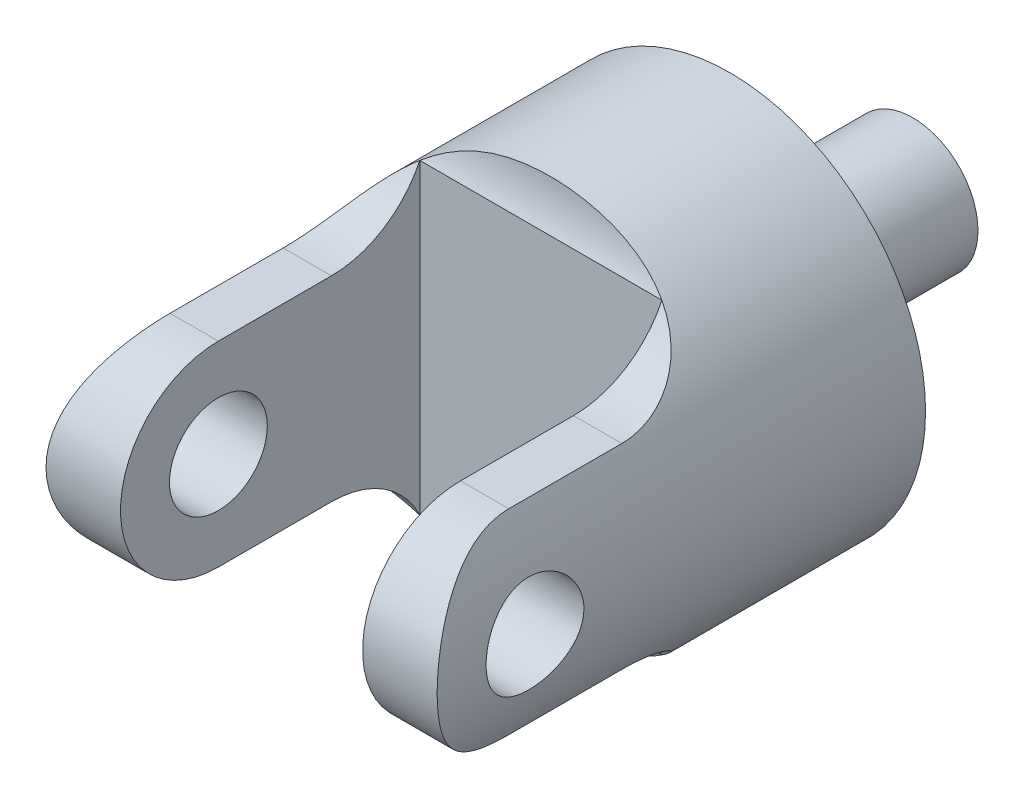
SolidWorks part; units mm, degrees
ref_plane "Front Plane" through (0, 0, 0) normal (0, 0, 1) x (1, 0, 0)
ref_plane "Top Plane" through (0, 0, 0) normal (0, 1, 0) x (1, 0, 0)
ref_plane "Right Plane" through (0, 0, 0) normal (1, 0, 0) x (0, 0, -1)
sketch "Sketch1" plane through (0, 0, 0) normal (0, 0, 1) x (1, 0, 0)
  circle A0 centre (0, 0) radius 6.35
  circle A1 centre (0, 0) radius 19.05
  dimension "D1" = 12.7
  dimension "D2" = 38.1
extrude "Boss-Extrude1" add sketch "Sketch1" along normal blind 47.57
extrude "Boss-Extrude2" add sketch "Sketch1<3>" along normal blind 18.42 and the other way blind 17.81 contours A0 region at (0, 0, 0)
sketch "Sketch1<3>" plane through (0, 0, 0) normal (0, 0, 1) x (1, 0, 0) same geometry as "Sketch1"
sketch "Sketch2" plane through (0, 0, 0) normal (0, 1, 0) x (1, 0, 0)
  line L0 (-11.79, -47.57) -> (11.79, -47.57)
  line L1 (-11.79, -47.57) -> (-11.79, -18.42)
  line L2 (11.79, -47.57) -> (11.79, -18.42)
  line L3 (-11.79, -18.42) -> (11.79, -18.42)
  line L4 (-19.05, -47.57) -> (19.05, -47.57) construction
  line L5 (19.05, 0) -> (-19.05, 0) construction
  dimension "D1" = 11.79
  dimension "D2" = 23.58
  dimension "D3" = 18.42
extrude "Cut-Extrude1" cut sketch "Sketch2" against normal through all both and the other way through all
sketch "Sketch3" plane through (0, 0, 0) normal (1, 0, 0) x (0, 0, -1)
  line L0 (0, 0) -> (-50000, 0) construction
  line L1 (-38.04, 9.53) -> (-36.8521, 9.53)
  line L2 (-50.2999, -9.53) -> (-38.04, -9.53)
  line L3 (-38.04, 9.53) -> (-68.1539, 9.53)
  line L4 (-68.0946, 9.165) -> (-59.6951, 20.2106)
  line L5 (-59.6951, 20.2106) -> (-27.0245, 19.06)
  line L6 (-68.0946, -9.165) -> (-59.6951, -20.2106)
  line L7 (-50.2999, -9.53) -> (-68.0946, -9.165)
  line L8 (-59.6951, -20.2106) -> (-27.0245, -19.06)
  line L9 (-47.57, 0) -> (-47.57, 9.53)
  line L10 (-47.57, 0) -> (-47.57, -9.586)
  line L13 (-47.57, 14.9632) -> (-47.57, -14.9632) construction
  line L14 (-38.04, -9.53) -> (-20.254, -9.53)
  line L15 (-38.04, 9.53) -> (-20.254, 9.53)
  line L16 (-50.2999, 9.53) -> (-38.04, 9.53)
  line L17 (-50.2999, 9.53) -> (-68.0946, 9.165)
  circle A0 centre (-38.04, 0) radius 4.765
  circle A1 centre (-38.04, 0) radius 9.53
  circle A3 centre (-27.0245, -19.06) radius 9.53
  circle A4 centre (-27.0245, 19.06) radius 9.53
  dimension "D1" = 9.53
  dimension "D2" = 19.06
  dimension "D3" = 19.06
extrude "Cut-Extrude2" cut sketch "Sketch3" against normal through all both and the other way through all contours A4 | A4 L5 L4 L3 L1 L15 | A3 | L8 A3 L14 L2 L7 L6 | A1 L3 L9 | A1 L10 L2 region at (0, 14.2462, 49.4177) region at (0, 7.4013, 45.4413) region at (0, -7.4013, 45.4413) region at (0, 12.6281, 33.6869) region at (0, -14.1953, 49.5508) region at (0, -12.5119, 20.4764)
sketch "Sketch4" plane through (0, 0, -17.81) normal (0, 0, -1) x (-1, 0, 0)
  line L0 (-4.203, -4.76) -> (4.203, -4.76)
  line L1 (-4.203, -4.76) -> (-3.709, -10.0855)
  line L2 (-3.709, -10.0855) -> (5.6397, -10.6444)
  line L3 (5.6397, -10.6444) -> (4.203, -4.76)
  circle A0 centre (0, 0) radius 6.35 construction
  point P4 (0, -4.76)
  dimension "D1" = 4.76
extrude "Cut-Extrude3" cut sketch "Sketch4" against normal blind 11.43
extrude "Cut-Extrude4" cut sketch "Sketch3<3>" against normal through all both and the other way through all contours A0 L0 | L0 A0 region at (0, -2.0223, 38.04) region at (0, 2.0223, 38.04)
sketch "Sketch3<3>" plane through (0, 0, 0) normal (1, 0, 0) x (0, 0, -1) same geometry as "Sketch3"
